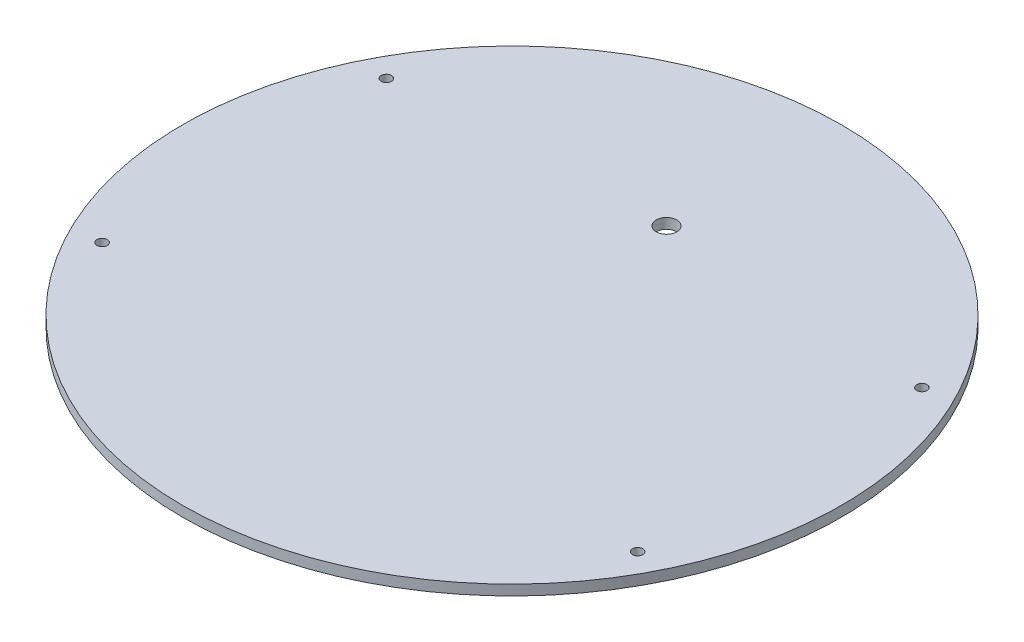
SolidWorks part; units mm, degrees
ref_plane "Front Plane" through (0, 0, 0) normal (0, 0, 1) x (1, 0, 0)
ref_plane "Top Plane" through (0, 0, 0) normal (0, 1, 0) x (1, 0, 0)
ref_plane "Right Plane" through (0, 0, 0) normal (1, 0, 0) x (0, 0, -1)
sketch "Sketch1" plane through (0, 0, 0) normal (0, 1, 0) x (1, 0, 0)
  circle A0 centre (0, 0) radius 101.6
  dimension "D1" = 203.2
extrude "Boss-Extrude1" add sketch "Sketch1" along normal blind 3.175
sketch "Sketch2" plane through (0, 3.175, 0) normal (0, 1, 0) x (1, 0, 0)
  line L0 (-82.55, 43.815) -> (-82.55, -43.815) construction
  line L1 (-82.55, -43.815) -> (82.55, -43.815) construction
  line L2 (82.55, -43.815) -> (82.55, 43.815) construction
  line L3 (82.55, 43.815) -> (-82.55, 43.815) construction
  circle A0 centre (-82.55, 43.815) radius 1.5875
  circle A1 centre (82.55, 43.815) radius 1.5875
  circle A2 centre (-82.55, -43.815) radius 1.5875
  circle A3 centre (82.55, -43.815) radius 1.5875
  dimension "D1" = 3.175
  dimension "D2" = 3.175
  dimension "D3" = 165.1
  dimension "D4" = 3.175
  dimension "D5" = 3.175
  dimension "D6" = 87.63
  dimension "D7" = 87.63
  dimension "D8" = 43.815
  dimension "D9" = 82.55
extrude "Cut-Extrude1" cut sketch "Sketch2" against normal up to next
sketch "Sketch3" plane through (0, 3.175, 0) normal (0, 1, 0) x (1, 0, 0)
  line L0 (0, 47.625) -> (0, 0) construction
  circle A0 centre (0, 47.625) radius 3.175
  dimension "D1" = 6.35
  dimension "D2" = 47.625
extrude "Cut-Extrude2" cut sketch "Sketch3" against normal up to next contours A0
ref_axis "Axis1" through (0, 3.175, 0) along (0, -1, 0)
